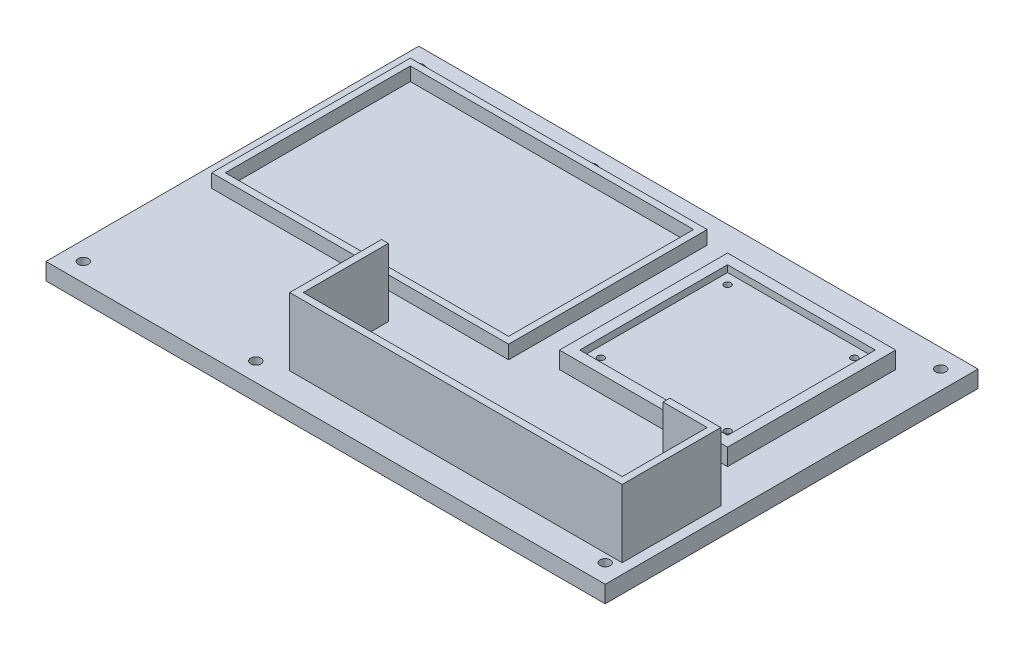
SolidWorks part; units mm, degrees
ref_plane "Front Plane" through (0, 0, 0) normal (0, 0, 1) x (1, 0, 0)
ref_plane "Top Plane" through (0, 0, 0) normal (0, 1, 0) x (1, 0, 0)
ref_plane "Right Plane" through (0, 0, 0) normal (1, 0, 0) x (0, 0, -1)
sketch "Sketch1" plane through (0, 0, 0) normal (0, 1, 0) x (1, 0, 0)
  line L1 (-82.5, -55) -> (82.5, -55)
  line L2 (-82.5, -55) -> (-82.5, 55)
  line L3 (-82.5, 55) -> (82.5, 55)
  line L4 (82.5, -55) -> (82.5, 55)
  line L5 (-82.5, -55) -> (82.5, 55) construction
  line L6 (-82.5, 55) -> (82.5, -55) construction
  point P0 (0, 0)
  dimension "D1" = 165
  dimension "D2" = 110
extrude "Boss-Extrude1" add sketch "Sketch1" along normal blind 5 contours L2 L1 L4 L3
sketch "Sketch4" plane through (0, 5, 0) normal (0, 1, 0) x (1, 0, 0)
  line L0 (82.5, -55) -> (82.5, 55) construction
  line L1 (-82.5, 55) -> (82.5, 55) construction
  line L2 (-82.5, -55) -> (-82.5, 55) construction
  line L3 (-82.5, -55) -> (82.5, -55) construction
  circle A0 centre (77, 49.5) radius 1.5
  circle A1 centre (-77, 49.5) radius 1.5
  circle A2 centre (-77, -49.5) radius 1.5
  circle A3 centre (77, -49.5) radius 1.5
  dimension "D3" = 3
  dimension "D6" = 3
  dimension "D9" = 3
  dimension "D12" = 3
  dimension "D1" = 5.5
  dimension "D2" = 5.5
  dimension "D4" = 5.5
  dimension "D5" = 5.5
  dimension "D7" = 5.5
  dimension "D8" = 5.5
  dimension "D10" = 5.5
  dimension "D11" = 5.5
extrude "Cut-Extrude1" cut sketch "Sketch4" against normal blind 10
sketch "Sketch5" plane through (0, 5, 0) normal (0, 1, 0) x (1, 0, 0)
  line L0 (82.5, -55) -> (82.5, 55) construction
  line L1 (77.5, -45) -> (-16.6, -45)
  line L2 (77.5, -45) -> (77.5, -19.9)
  line L3 (77.5, -19.9) -> (-16.6, -19.9)
  line L4 (-16.6, -45) -> (-16.6, -19.9)
  line L5 (-82.5, -55) -> (82.5, -55) construction
  line L6 (-16.6, -19.9) -> (-18.6, -19.9)
  line L7 (-18.6, -17.9) -> (79.5, -17.9)
  line L8 (-18.6, -17.9) -> (-18.6, -47)
  line L9 (-18.6, -47) -> (79.5, -47)
  line L10 (79.5, -17.9) -> (79.5, -47)
  line L12 (64.5, -19.9) -> (64.5, -17.9)
  dimension "D1" = 5
  dimension "D2" = 10
  dimension "D3" = 25.1
  dimension "D4" = 94.1
  dimension "D5" = 2
  dimension "D6" = 2
  dimension "D7" = 2
  dimension "D8" = 2
  dimension "D9" = 15
extrude "Boss-Extrude2" add sketch "Sketch5" along normal blind 20 contours L2 L1 L4 L6 L8 L9 L10 region at (78.5233, 5, 32.45)
sketch "Sketch7" plane through (0, 5, 0) normal (0, 1, 0) x (1, 0, 0)
  line L1 (23.9, 39.7) -> (67.5, 39.7)
  line L2 (23.9, 39.7) -> (23.9, -3.9)
  line L3 (23.9, -3.9) -> (67.5, -3.9)
  line L4 (67.5, 39.7) -> (67.5, -3.9)
  line L5 (64.5, -17.9) -> (79.5, -17.9) construction
  line L7 (20.9, 42.7) -> (70.5, 42.7)
  line L8 (20.9, 42.7) -> (20.9, -6.9)
  line L9 (20.9, -6.9) -> (70.5, -6.9)
  line L10 (70.5, 42.7) -> (70.5, -6.9)
  dimension "D1" = 43.6
  dimension "D2" = 43.6
  dimension "D4" = 14
  dimension "D5" = 3
  dimension "D6" = 3
  dimension "D7" = 3
  dimension "D8" = 3
extrude "Boss-Extrude3" add sketch "Sketch7" along normal blind 3 contours L2 L1 L4 L3
extrude "Boss-Extrude4" add sketch "Sketch7<3>" along normal blind 5
sketch "Sketch7<3>" plane through (0, 5, 0) normal (0, 1, 0) x (1, 0, 0) same geometry as "Sketch7"
sketch "Sketch8" plane through (0, 5, 0) normal (0, 1, 0) x (1, 0, 0)
  line L0 (23.9, 39.7) -> (23.9, -3.9) construction
  line L1 (-74.7, 44.7) -> (8.9, 44.7)
  line L2 (-74.7, 44.7) -> (-74.7, -9.9)
  line L3 (-74.7, -9.9) -> (8.9, -9.9)
  line L4 (8.9, 44.7) -> (8.9, -9.9)
  line L5 (-16.6, -19.9) -> (-18.6, -19.9) construction
  line L7 (-76.7, 46.7) -> (10.9, 46.7)
  line L8 (-76.7, 46.7) -> (-76.7, -11.9)
  line L9 (-76.7, -11.9) -> (10.9, -11.9)
  line L10 (10.9, 46.7) -> (10.9, -11.9)
  dimension "D1" = 15
  dimension "D2" = 54.6
  dimension "D3" = 83.6
  dimension "D4" = 10
  dimension "D5" = 2
  dimension "D6" = 2
  dimension "D7" = 2
  dimension "D8" = 2
extrude "Boss-Extrude5" add sketch "Sketch8" along normal blind 4
sketch "Sketch9" plane through (0, 5, 0) normal (0, 1, 0) x (1, 0, 0)
  line L0 (-18.6, -19.9) -> (-18.6, -47) construction
  line L1 (-82.5, -55) -> (82.5, -55) construction
  line L2 (-18.6, -19.9) -> (-18.6, -47) construction
  line L3 (-82.5, 55) -> (82.5, 55) construction
  circle A0 centre (-26.1, -49.5) radius 1.5
  circle A1 centre (-26.1, 49.5) radius 1.5
  dimension "D3" = 3
  dimension "D6" = 3
  dimension "D1" = 7.5
  dimension "D2" = 5.5
  dimension "D4" = 7.5
  dimension "D5" = 5.5
extrude "Cut-Extrude2" cut sketch "Sketch9" against normal blind 5
sketch "Sketch10" plane through (0, 8, 0) normal (0, 1, 0) x (1, 0, 0)
  line L0 (27, 39.7) -> (27, 36.6) construction
  line L1 (23.9, 39.7) -> (67.5, 39.7) construction
  line L2 (27, 36.6) -> (23.9, 36.6) construction
  line L3 (23.9, 39.7) -> (23.9, -3.9) construction
  line L5 (45.7, 39.7) -> (45.7, -3.9) construction
  line L6 (23.9, -3.9) -> (67.5, -3.9) construction
  circle A0 centre (27, 36.6) radius 1
  circle A1 centre (27, -0.8) radius 1
  circle A2 centre (64.4, -0.8) radius 1
  circle A3 centre (64.4, 36.6) radius 1
  dimension "D3" = 2
  dimension "D1" = 3.1
  dimension "D2" = 3.1
  dimension "D4" = 2
extrude "Cut-Extrude3" cut sketch "Sketch10" against normal through all
